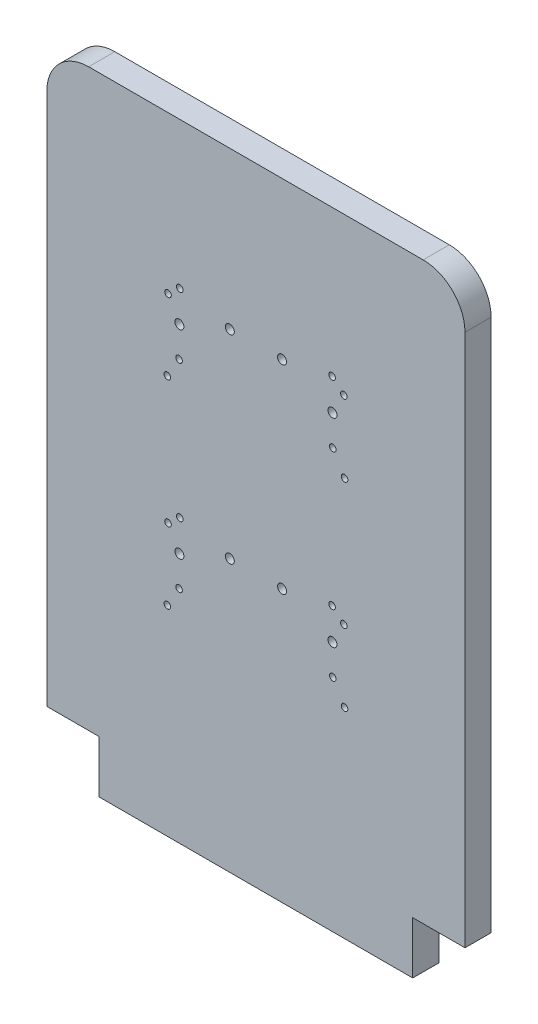
SolidWorks part; units mm, degrees
ref_plane "Front Plane" through (0, 0, 0) normal (0, 0, 1) x (1, 0, 0)
ref_plane "Top Plane" through (0, 0, 0) normal (0, 1, 0) x (1, 0, 0)
ref_plane "Right Plane" through (0, 0, 0) normal (1, 0, 0) x (0, 0, -1)
sketch "Sketch1" plane through (0, 0, 0) normal (0, 0, 1) x (1, 0, 0)
  line L0 (88.9, 0) -> (101.6, 0)
  line L1 (0, 0) -> (12.7, 0)
  line L2 (0, 0) -> (0, 139.7)
  line L3 (0, 139.7) -> (101.6, 139.7)
  line L4 (101.6, 0) -> (101.6, 139.7)
  line L6 (12.7, 0) -> (12.7, -12.7)
  line L7 (12.7, -12.7) -> (88.9, -12.7)
  line L8 (88.9, 0) -> (88.9, -12.7)
  line L9 (50.8, -12.7) -> (50.8, 139.7) construction
  circle A0 centre (44.45, 53.34) radius 1.0922
  circle A1 centre (57.15, 53.34) radius 1.0922
  circle A2 centre (32.3, 55.88) radius 0.8
  circle A3 centre (69.3, 55.88) radius 0.8
  circle A4 centre (32.1253, 40.88) radius 0.8
  circle A6 centre (69.4747, 40.88) radius 0.8
  circle A7 centre (32.3, 104.14) radius 0.8
  circle A8 centre (32.1253, 89.14) radius 0.8
  circle A9 centre (69.4747, 89.14) radius 0.8
  circle A10 centre (69.3, 104.14) radius 0.8
  circle A11 centre (44.45, 101.6) radius 1.0922
  circle A12 centre (57.15, 101.6) radius 1.0922
  circle A13 centre (29.4386, 53.34) radius 0.8
  circle A14 centre (29.2639, 35.954) radius 0.8
  circle A15 centre (72.3361, 35.954) radius 0.8
  circle A16 centre (72.1614, 53.34) radius 0.8
  circle A17 centre (29.4386, 101.6) radius 0.8
  circle A18 centre (29.2639, 84.214) radius 0.8
  circle A19 centre (72.3361, 84.214) radius 0.8
  circle A20 centre (72.1614, 101.6) radius 0.8
  circle A21 centre (32.2, 48.26) radius 1.0922
  circle A22 centre (69.4, 48.26) radius 1.0922
  circle A23 centre (32.2, 96.52) radius 1.0922
  circle A24 centre (69.4, 96.52) radius 1.0922
  dimension "D6" = 6.35
  dimension "D8" = 18.5
  dimension "D17" = 18.6
  dimension "D1" = 139.7
  dimension "D2" = 101.6
  dimension "D3" = 12.7
  dimension "D4" = 76.2
  dimension "D5" = 12.7
  dimension "D7" = 66.04
  dimension "D9" = 15
  dimension "D12" = 68.58
  dimension "D13" = 17.386
  dimension "D14" = 21.3614
  dimension "D15" = 66.04
  dimension "D18" = 60.96
  dimension "D10" = 2
  dimension "D11" = 2
  dimension "D16" = 2
  dimension "D19" = 2
extrude "Boss-Extrude1" add sketch "Sketch1" along normal blind 6.35
fillet "Fillet1" radius 10.16 2 edges at (101.6, 139.7, 3.175) (0, 139.7, 3.175)
